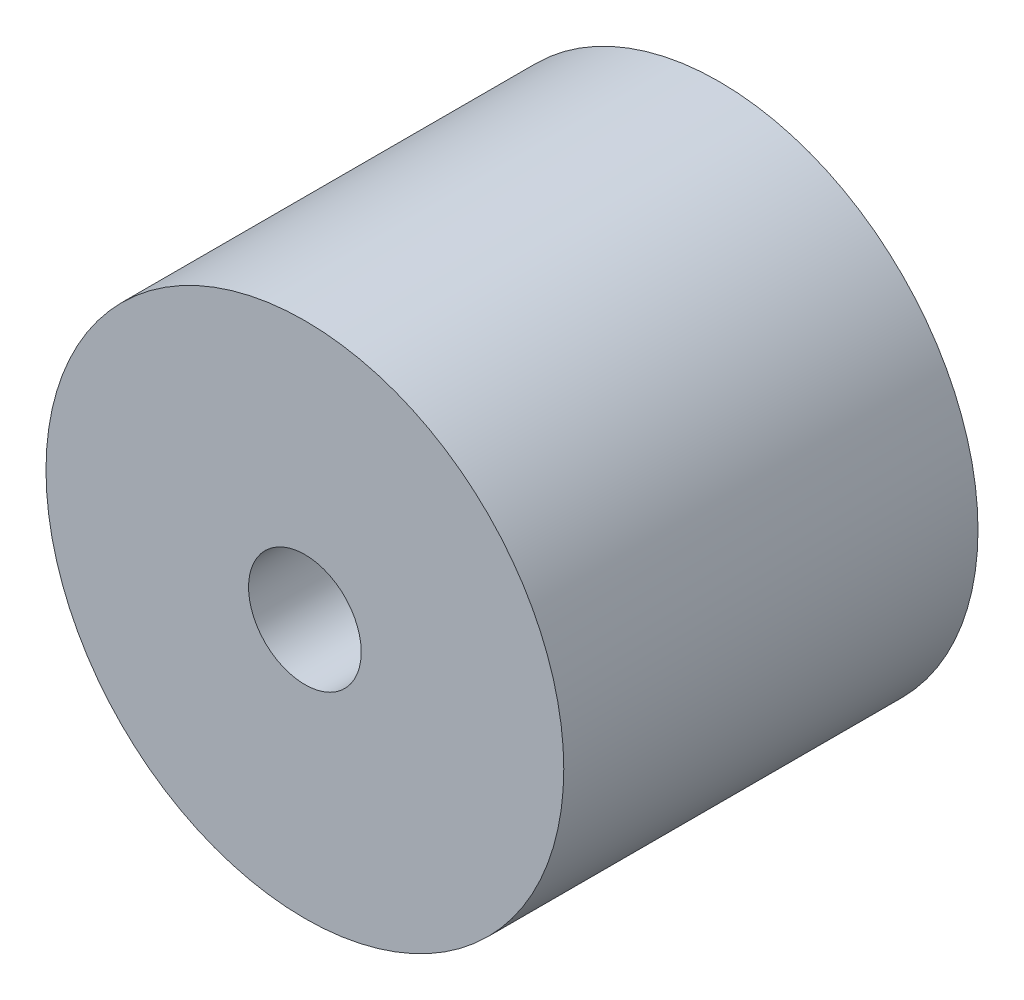
SolidWorks part; units mm, degrees
ref_plane "Front Plane" through (0, 0, 0) normal (0, 0, 1) x (1, 0, 0)
ref_plane "Top Plane" through (0, 0, 0) normal (0, 1, 0) x (1, 0, 0)
ref_plane "Right Plane" through (0, 0, 0) normal (1, 0, 0) x (0, 0, -1)
sketch "Sketch1" plane through (0, 0, 0) normal (0, 0, 1) x (1, 0, 0)
  circle A0 centre (0, 0) radius 7.9375
  dimension "D1" = 15.875
extrude "Boss-Extrude1" add sketch "Sketch1" along normal blind 12.7
hole_wizard "#8-32 Tapped Hole1" positions "Sketch4" profile "Sketch5" tap size "#8-32" standard "Ansi Inch" end condition through all
sketch "Sketch4" plane through (0, 0, 12.7) normal (0, 0, 1) x (1, 0, 0)
  point P0 (0, 0)
sketch "Sketch5" plane through (0, 0, 12.7) normal (1, 0, 0) x (0, -1, 0)
  line L0 (0, 0) -> (0, 12.7)
  line L1 (0, 12.7) -> (1.7272, 12.7)
  line L2 (1.7272, 12.7) -> (1.7272, 0)
  line L5 (1.7272, 0) -> (0, 0)
  line L11 (0, -6.35) -> (0, 107.95) construction
  dimension "Thru Tap Drill Dia." = 3.4544
  dimension "Thru Tap Drill Depth" = 12.7
cosmetic thread "Hole Thread1" parameters "D2"=4.1656
